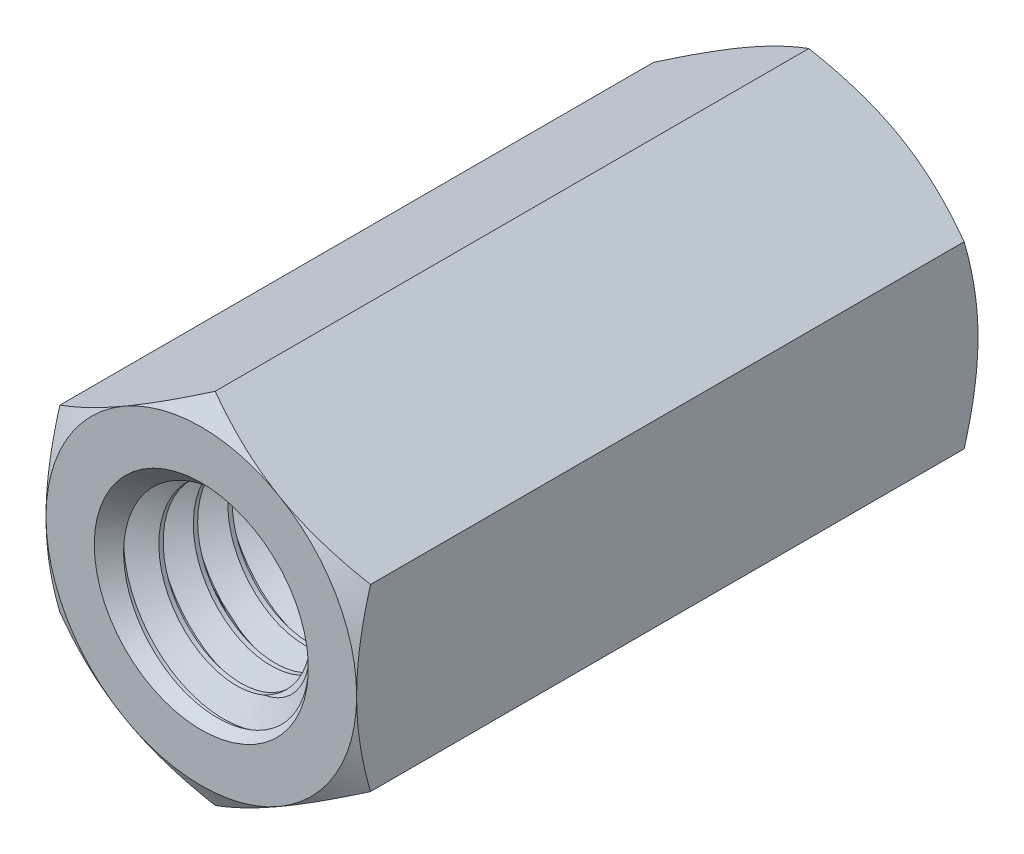
SolidWorks part; units mm, degrees
ref_plane "Front Plane" through (0, 0, 0) normal (0, 0, 1) x (1, 0, 0)
ref_plane "Top Plane" through (0, 0, 0) normal (0, 1, 0) x (1, 0, 0)
ref_plane "Right Plane" through (0, 0, 0) normal (1, 0, 0) x (0, 0, -1)
sketch "Sketch3" plane through (0, 0, 0) normal (1, 0, 0) x (0, 0, -1)
  line L0 (-4.5, 0) -> (4.5, 0) construction
  line L1 (0, 2.25) -> (0, -2.25) construction
  line L2 (-4.5, 1.5) -> (-4.5, -1.5) construction
  point P2 (-8.2, 0)
  point P3 (8.2, 0)
  dimension "D1" = 12.7
  dimension "Length" = 9
  dimension "Min Thread Length" = 12.7
  dimension "Thread Dia" = 3
  dimension "Hex" = 4.5
sketch "Sketch1" plane through (0, 0, 0) normal (0, 0, 1) x (1, 0, 0)
  line L1 (0, 2.5981) -> (-2.25, 1.299)
  line L2 (-2.25, 1.299) -> (-2.25, -1.299)
  line L3 (-2.25, -1.299) -> (0, -2.5981)
  line L4 (0, -2.5981) -> (2.25, -1.299)
  line L5 (2.25, -1.299) -> (2.25, 1.299)
  line L6 (2.25, 1.299) -> (0, 2.5981)
  circle A0 centre (0, 0) radius 2.25 construction
  circle A1 centre (0, 0) radius 1.5
extrude "Extrude1" add sketch "Sketch1" along normal up to vertex (4.5 mm away) and the other way up to vertex (4.5 mm away) up to point (0, 0, 4.5) other way up to point (0, 0, -4.5)
sketch "Sketch11" plane through (0, 0, -4.5) normal (0, 0, -1) x (-1, 0, 0)
  circle A0 centre (0, 0) radius 1.5 construction
  circle A1 centre (0, 0) radius 1.5
curve "Helix/Spiral1" pitch 0.5 height 9.5 radius 1.5 centre (0, 0, -4.5) axis (0, 0, 1) start towards (0, 1, 0) parameters "Pitch"=0.5
sketch "Sketch12" plane through (0, 0, 0) normal (1, 0, 0) x (0, 0, -1)
  line L0 (4.9375, 1.5) -> (4.5, 1.5)
  line L1 (4.9375, 1.5) -> (4.75, 1.1752)
  line L2 (4.75, 1.1752) -> (4.6875, 1.1752)
  line L3 (4.6875, 1.1752) -> (4.5, 1.5)
  line L4 (4.7188, 1.1752) -> (4.7188, 1.5) construction
  line L5 (4.8438, 1.3376) -> (4.5938, 1.3376) construction
  dimension "D1" = 0.0625
  dimension "D2" = 0.25
  dimension "D3" = 60
sweep "Sweep1" add profiles "Sketch12" path "Helix/Spiral1"
sketch "Sketch6" plane through (0, 0, -4.5) normal (0, 0, -1) x (-1, 0, 0)
  line L6 (0, 2.5981) -> (-2.25, 1.299)
  line L7 (-2.25, 1.299) -> (-2.25, -1.299)
  line L8 (-2.25, -1.299) -> (0, -2.5981)
  line L9 (0, -2.5981) -> (2.25, -1.299)
  line L10 (2.25, -1.299) -> (2.25, 1.299)
  line L11 (2.25, 1.299) -> (0, 2.5981)
  line L12 (0, 2.5981) -> (-2.25, 1.299)
  line L13 (-2.25, 1.299) -> (-2.25, -1.299)
  line L14 (-2.25, -1.299) -> (0, -2.5981)
  line L15 (0, -2.5981) -> (2.25, -1.299)
  line L16 (2.25, -1.299) -> (2.25, 1.299)
  line L17 (2.25, 1.299) -> (0, 2.5981)
  dimension "D1" = 0
extrude "Extrude2" cut sketch "Sketch6" along normal through all
sketch "Sketch7" plane through (0, 0, -4.5) normal (0, 0, -1) x (-1, 0, 0)
  circle A2 centre (0, 0) radius 1.5508
  circle A3 centre (0, 0) radius 1.5508
  dimension "D1" = 0.0508
extrude "Extrude3" cut sketch "Sketch7" against normal through all draft 43
sketch "Sketch8" plane through (0, 0, -4.5) normal (0, 0, -1) x (-1, 0, 0)
  circle A0 centre (0, 0) radius 2.25 construction
  circle A1 centre (0, 0) radius 2.25
extrude "Extrude4" cut sketch "Sketch8" against normal through all draft 60 flip side to cut
mirror "Mirror1" about plane through (0, 0, 0) normal (0, 0, 1) of "Extrude2", "Extrude3", "Extrude4"
sketch "Sketch9" [suppressed] plane through (0, 0, 0) normal (1, 0, 0) x (0, 0, -1)
  line L1 (-12.7, 2.4638) -> (12.7, 2.4638)
  line L2 (-12.7, 2.4638) -> (-12.7, 0)
  line L3 (-12.7, 0) -> (12.7, 0)
  line L4 (12.7, 2.4638) -> (12.7, 0)
  line L7 (-25.4, 0) -> (25.4, 0) construction
revolve "Revolve" [suppressed] add sketch "Sketch9" angle 360 about L0
sketch "Sketch10" [suppressed] plane through (0, 0, 0) normal (1, 0, 0) x (0, 0, -1)
  line L0 (25.4, 2.413) -> (12.7, 2.413)
  line L1 (-25.4, 2.413) -> (-12.7, 2.413)
  line L2 (12.7, 2.413) -> (12.7, -2.413)
  line L3 (-25.4, -2.4638) -> (-12.7, -2.4638)
  line L4 (-12.7, 2.413) -> (-12.7, -2.4638)
  line L5 (12.7, -2.413) -> (25.4, -2.413)
sketch "Sketch13" plane through (0, 0, 4.5) normal (0, 0, 1) x (1, 0, 0)
  line L0 (0.6959, 0.4402) -> (1.0897, 0.4402) construction
  line L1 (0.6959, 0.4402) -> (0.6959, -0.3853) construction
  line L2 (0.6959, 0.4402) -> (3.8103, 3.3481) construction
  arc A0 (0.5013, -1.063) -> (1.1082, -0.3912) centre (0, 0) ccw construction
  point P0 (0.6959, 0.4402)
  point P8 (-11.7542, 6.7404)
  point P9 (3.8103, 3.3481)
  point P10 (3.8103, 3.3481)
  point P11 (1.0897, 0.4402)
equation "\"D1@Sketch3\" = \"Min Thread Length@Sketch3\""
equation "\"D3@Helix/Spiral1\" = \"Length@Sketch3\"+\"Pitch@Helix/Spiral1\""
equation "\"D1@Sketch12\" = \"Pitch@Helix/Spiral1\"*.125"
equation "\"D2@Sketch12\" = \"Pitch@Helix/Spiral1\"*.5"
